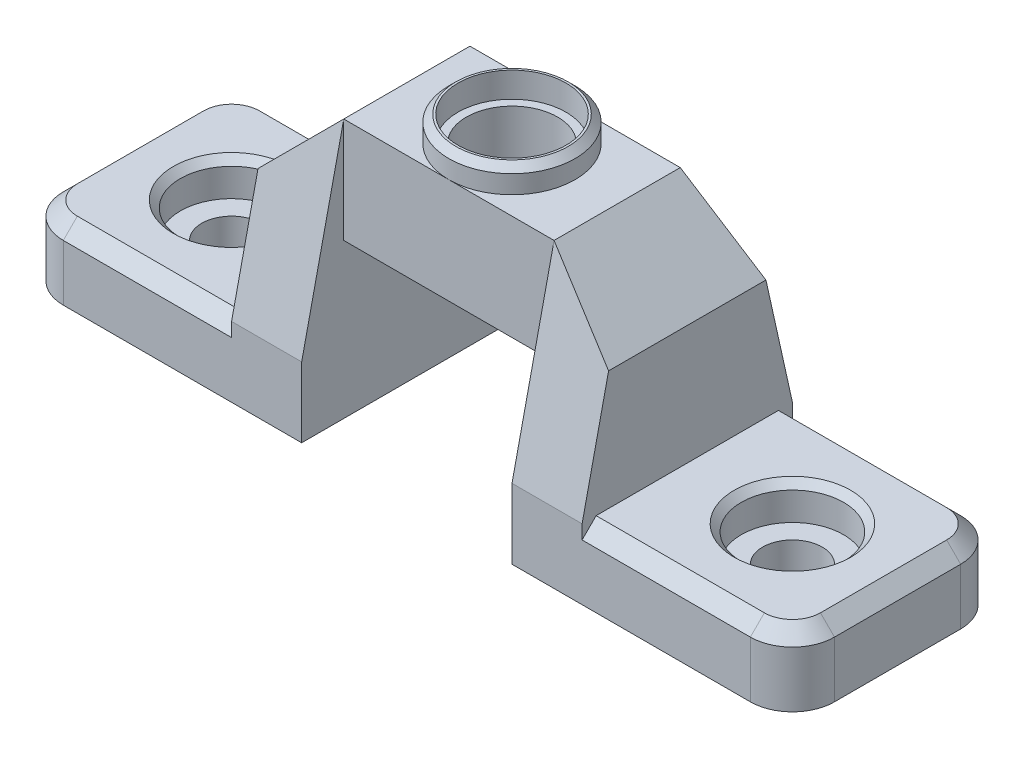
SolidWorks part; units mm, degrees
ref_plane "Front Plane" through (0, 0, 0) normal (0, 0, 1) x (1, 0, 0)
ref_plane "Top Plane" through (0, 0, 0) normal (0, 1, 0) x (1, 0, 0)
ref_plane "Right Plane" through (0, 0, 0) normal (1, 0, 0) x (0, 0, -1)
sketch "Sketch1" plane through (0, 0, 0) normal (0, 0, 1) x (1, 0, 0)
  line L0 (0, 0) -> (20, 0)
  line L1 (20, 0) -> (20, 10)
  line L2 (20, 10) -> (35, 10)
  line L3 (35, 10) -> (35, 0)
  line L4 (35, 0) -> (55, 0)
  line L5 (55, 0) -> (55, 5)
  line L6 (55, 5) -> (40, 5)
  line L7 (40, 5) -> (40, 18.5)
  line L8 (40, 18.5) -> (15, 18.5)
  line L9 (15, 18.5) -> (15, 5)
  line L10 (15, 5) -> (0, 5)
  line L11 (0, 5) -> (0, 0)
  point P11 (20, 5)
  dimension "D1" = 20
  dimension "D2" = 5
  dimension "D3" = 5
  dimension "D4" = 5
  dimension "D5" = 15
  dimension "D6" = 8.5
  dimension "D7" = 10
extrude "Boss-Extrude1" add sketch "Sketch1" along normal blind 15
sketch "Sketch2" plane through (0, 0, 15) normal (0, 0, 1) x (1, 0, 0)
  line L1 (15, 18.5) -> (40, 18.5)
  line L2 (15, 18.5) -> (15, 5)
  line L3 (15, 5) -> (40, 5)
  line L4 (40, 18.5) -> (40, 5)
extrude "Cut-Extrude1" cut sketch "Sketch2" against normal blind 3
sketch "Sketch3" plane through (0, 0, 0) normal (0, 0, -1) x (-1, 0, 0)
  line L1 (-40, 18.5) -> (-15, 18.5)
  line L2 (-40, 18.5) -> (-40, 5)
  line L3 (-40, 5) -> (-15, 5)
  line L4 (-15, 18.5) -> (-15, 5)
extrude "Cut-Extrude2" cut sketch "Sketch3" against normal blind 3
sketch "Sketch4" plane through (20, 0, 0) normal (1, 0, 0) x (0, 0, -1)
  line L0 (-12, 18.5) -> (-15, 5)
  line L1 (-15, 5) -> (-12, 5)
  line L2 (-12, 5) -> (-12, 18.5)
  line L3 (-3, 5) -> (0, 5)
  line L4 (0, 5) -> (-3, 18.5)
  line L5 (-3, 18.5) -> (-3, 5)
extrude "Boss-Extrude2" add sketch "Sketch4" against normal up to surface (5 mm away) up to face at (15, 11.75, 7.5)
sketch "Sketch5" plane through (35, 0, 0) normal (-1, 0, 0) x (0, 0, 1)
  line L0 (0, 5) -> (3, 18.5)
  line L1 (3, 18.5) -> (3, 5)
  line L2 (15, 5) -> (0, 5) construction
  line L3 (3, 5) -> (0, 5)
  line L4 (12, 18.5) -> (12, 5)
  line L5 (15, 5) -> (0, 5) construction
  line L6 (12, 5) -> (15, 5)
  line L7 (15, 5) -> (12, 18.5)
extrude "Boss-Extrude3" add sketch "Sketch5" against normal up to surface (5 mm away) up to face at (40, 11.75, 7.5)
sketch "Sketch6" plane through (0, 18.5, 0) normal (0, 1, 0) x (1, 0, 0)
  line L0 (15, -7.5) -> (40, -7.5) construction
  line L1 (15, -12) -> (15, -3) construction
  line L2 (40, -12) -> (40, -3) construction
  circle A0 centre (27.5, -7.5) radius 3.25
  dimension "D1" = 6.5
extrude "Cut-Extrude3" cut sketch "Sketch6" against normal up to surface (8.5 mm away) up to face at (27.5, 10, 7.5)
sketch "Sketch7" plane through (0, 5, 0) normal (0, 1, 0) x (1, 0, 0)
  line L0 (0, -7.5) -> (15, -7.5) construction
  line L1 (0, -15) -> (0, 0) construction
  line L2 (15, -15) -> (15, 0) construction
  line L3 (40, -7.5) -> (55, -7.5) construction
  line L4 (40, -12) -> (40, -3) construction
  line L5 (55, -15) -> (55, 0) construction
  circle A0 centre (7.5, -7.5) radius 2.125
  circle A1 centre (47.5, -7.5) radius 2.125
  dimension "D1" = 4.25
extrude "Cut-Extrude4" cut sketch "Sketch7" against normal up to surface (5 mm away) up to face at (10, 0, 7.5)
sketch "Sketch8" plane through (0, 5, 0) normal (0, 1, 0) x (1, 0, 0)
  circle A0 centre (7.5, -7.5) radius 3.65
  circle A1 centre (47.5, -7.5) radius 3.65
  dimension "D1" = 7.3
extrude "Cut-Extrude5" cut sketch "Sketch8" against normal blind 2.5
chamfer "Chamfer3" distance 0.5 angle 45 2 edges at (43.85, 5, 7.5) (3.85, 5, 7.5)
fillet "Fillet1" radius 3 4 edges at (0, 2.5, 0) (0, 2.5, 15) (55, 2.5, 0) (55, 2.5, 15)
sketch "Sketch9" plane through (0, 18.5, 0) normal (0, 1, 0) x (1, 0, 0)
  line L0 (20, -3) -> (35, -3) construction
  circle A0 centre (27.5, -7.5) radius 3.85
  circle A1 centre (27.5, -7.5) radius 4.5
  dimension "D1" = 7.7
extrude "Boss-Extrude4" add sketch "Sketch9" along normal blind 1.8
chamfer "Chamfer4" distance 5 angle 45 2 edges at (40, 18.5, 7.5) (15, 18.5, 7.5)
chamfer "Chamfer5" distance 1 angle 45 12 edges at (9, 5, 15) (0.8787, 5, 14.1213) (0, 5, 7.5) (0.8787, 5, 0.8787) (9, 5, 0) (46, 5, 15) (54.1213, 5, 14.1213) (55, 5, 7.5) (54.1213, 5, 0.8787) (46, 5, 0) (27.5, 10, 3) (27.5, 10, 12)
chamfer "Chamfer6" distance 0.5 angle 45 1 edges at (23, 20.3, 7.5)
